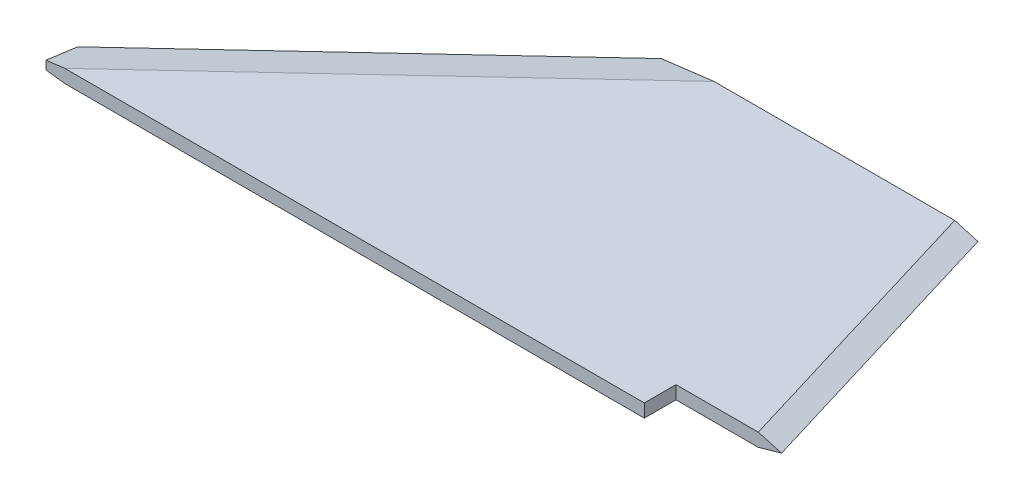
SolidWorks part; units mm, degrees
ref_plane "Front Plane" through (0, 0, 0) normal (0, 0, 1) x (1, 0, 0)
ref_plane "Top Plane" through (0, 0, 0) normal (0, 1, 0) x (1, 0, 0)
ref_plane "Right Plane" through (0, 0, 0) normal (1, 0, 0) x (0, 0, -1)
sketch "Sketch2" plane through (0, 0, 0) normal (0, 1, 0) x (1, 0, 0)
  line L0 (0, 0) -> (254, 0)
  line L1 (0, 0) -> (0, 132.7069)
  line L2 (0, 0) -> (108.966, 101.6124)
  line L3 (108.966, 101.6124) -> (223.266, 101.6124)
  line L5 (223.266, 101.6124) -> (254, 0)
  line L6 (0, 0) -> (215.9, 0)
  line L7 (0, 0) -> (0, -11.43)
  line L8 (0, -11.43) -> (215.9, -11.43)
  line L9 (215.9, 0) -> (215.9, -11.43)
  dimension "D1" = 254
  dimension "D2" = 47
  dimension "D3" = 114.3
  dimension "D4" = 108.966
  dimension "D5" = 101.6124
  dimension "D6" = 11.43
  dimension "D7" = 215.9
extrude "Boss-Extrude1" add sketch "Sketch2" along normal blind 4.7498 contours L2 L3 L5 L0 | L7 L6 L9 L8
ref_plane "Plane4" through (108.966, 0, -101.6124) normal (-0.7314, 0, 0.682) x (0.682, 0, 0.7314)
sketch "Sketch9" plane through (108.966, 0, -101.6124) normal (-0.7314, 0, 0.682) x (0.682, 0, 0.7314)
  line L0 (0, 2.3749) -> (12.9927, 0)
  line L1 (0, 4.7498) -> (0, 0) construction
  line L2 (0, 0) -> (8.3594, 0) construction
  line L4 (0, 4.7498) -> (8.3594, 4.7498) construction
  line L5 (12.9927, 4.7498) -> (0, 2.3749)
  line L6 (12.9927, 4.7498) -> (12.9927, 7.4487)
  line L7 (12.9927, 7.4487) -> (-2.3775, 7.4487)
  line L8 (-2.3775, 7.4487) -> (-2.3775, -1.9753)
  line L9 (-2.3775, -1.9753) -> (12.9927, -1.9753)
  line L10 (12.9927, -1.9753) -> (12.9927, 0)
  dimension "D1" = 13.208
  dimension "D2" = 20.717
ref_plane "Plane5" through (21.2893, 0, 70.3864) normal (-0.2895, 0, -0.9572) x (-0.9572, 0, 0.2895)
sketch "Sketch11" plane through (21.2893, 0, 70.3864) normal (-0.2895, 0, -0.9572) x (-0.9572, 0, 0.2895)
  line L0 (-243.1224, 2.3749) -> (-235.0839, 4.7498)
  line L1 (-243.1224, 4.7498) -> (-243.1224, 0) construction
  line L2 (-133.7173, 4.7498) -> (-243.1224, 4.7498) construction
  line L4 (-133.7173, 0) -> (-243.1224, 0) construction
  line L5 (-235.0839, 0) -> (-243.1224, 2.3749)
  line L6 (-235.0839, 4.7498) -> (-235.0839, 6.7357)
  line L7 (-235.0839, 6.7357) -> (-246.0086, 6.7357)
  line L8 (-235.0839, 0) -> (-235.0839, -1.6837)
  line L9 (-235.0839, -1.6837) -> (-246.0086, -1.6837)
  line L10 (-246.0086, -1.6837) -> (-246.0086, 6.7357)
  dimension "D1" = 8.382
  dimension "D2" = 32.918
extrude "Cut-Extrude1" cut sketch "Sketch11" along normal blind 127 contours L7 L10 L9 L8 L5 L0 L6
extrude "Cut-Extrude2" cut sketch "Sketch9" against normal through all both and the other way through all
